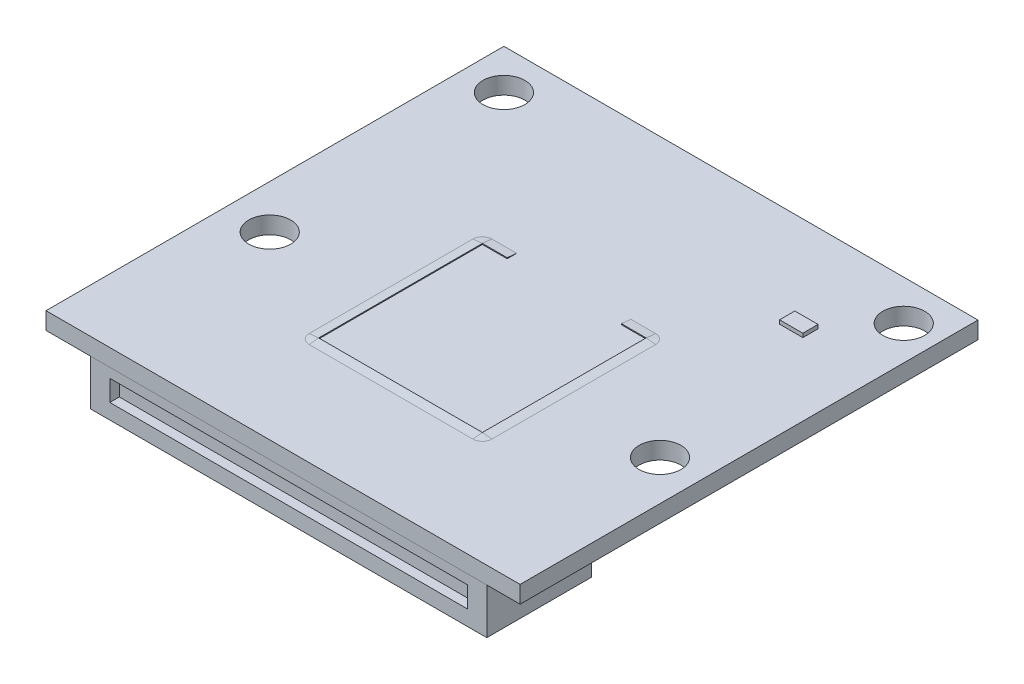
SolidWorks part; units mm, degrees
ref_plane "Front" through (0, 0, 0) normal (0, 0, 1) x (1, 0, 0)
ref_plane "Top" through (0, 0, 0) normal (0, 1, 0) x (1, 0, 0)
ref_plane "Right" through (0, 0, 0) normal (1, 0, 0) x (0, 0, -1)
sketch "Skizze1" plane through (0, 0, 0) normal (0, 1, 0) x (1, 0, 0)
  line L0 (-0.3, 13.88) -> (-0.3, -10.17) construction
  line L1 (-12.75, 13.88) -> (12.15, 13.88)
  line L2 (-12.75, 13.88) -> (-12.75, -10.17)
  line L3 (-12.75, -10.17) -> (12.15, -10.17)
  line L4 (12.15, 13.88) -> (12.15, -10.17)
  line L5 (0, 4.3) -> (0, -4.3) construction
  line L6 (-4.3, 0) -> (4.3, 0) construction
  line L7 (-4.3, 4.3) -> (4.3, 4.3) construction
  line L8 (-4.3, 4.3) -> (-4.3, -4.3) construction
  line L9 (-4.3, -4.3) -> (4.3, -4.3) construction
  line L10 (4.3, 4.3) -> (4.3, -4.3) construction
  circle A0 centre (-10.65, 11.78) radius 1.1
  circle A1 centre (10.35, 11.78) radius 1.1
  circle A2 centre (-10.45, -0.72) radius 1.1
  circle A3 centre (10.05, -0.72) radius 1.1
  dimension "D4" = 2.2
  dimension "D1" = 24.05
  dimension "D2" = 24.9
  dimension "D5" = 21
  dimension "D7" = 20.5
  dimension "D8" = 1.8
  dimension "D9" = 2.1
  dimension "D10" = 2.1
  dimension "D11" = 12.5
  dimension "D12" = 16.45
  dimension "D13" = 17.05
  dimension "D14" = 18.18
extrude "PCB" add sketch "Skizze1" against normal blind 0.9
sketch "Sketch4" plane through (0, 0, 0) normal (0, 1, 0) x (1, 0, 0)
  line L0 (-4.3, 4.3) -> (4.3, 4.3) construction
  line L1 (4.3, 4.3) -> (4.3, -4.3) construction
  line L2 (-4.3, -4.3) -> (4.3, -4.3) construction
  line L3 (-4.3, 4.3) -> (-4.3, -4.3) construction
  line L4 (-4.3, 4.3) -> (-3, 4.3)
  line L5 (4.3, 4.3) -> (4.3, -4.3)
  line L6 (-4.3, -4.3) -> (4.3, -4.3)
  line L7 (-4.3, 4.3) -> (-4.3, -4.3)
  line L8 (-4.8, 4.8) -> (-3, 4.8)
  line L9 (4.8, 4.8) -> (4.8, -4.8)
  line L10 (-4.8, -4.8) -> (4.8, -4.8)
  line L11 (-4.8, 4.8) -> (-4.8, -4.8)
  line L12 (-3, 4.8) -> (-3, 4.3)
  line L13 (3, 4.8) -> (3, 4.3)
  line L14 (0, 0) -> (0, 4.3) construction
  line L15 (3, 4.3) -> (4.3, 4.3)
  line L16 (-4.3, 4.3) -> (4.3, 4.3) construction
  line L17 (3, 4.8) -> (4.8, 4.8)
  line L18 (-4.8, 4.8) -> (4.8, 4.8) construction
  dimension "D2" = 6
  dimension "D1" = 0.5
extrude "Boss-Extrude1" add sketch "Sketch4" along normal blind 0.05
sketch "Skizze3" plane through (0, -0.9, 0) normal (0, -1, 0) x (1, 0, 0)
  line L0 (0, 4.67) -> (0, 0) construction
  line L1 (-10.4, 10.17) -> (10.4, 10.17)
  line L2 (-10.4, 10.17) -> (-10.4, 4.67)
  line L3 (-10.4, 4.67) -> (10.4, 4.67)
  line L4 (10.4, 10.17) -> (10.4, 4.67)
  line L5 (-12.75, 10.17) -> (12.15, 10.17) construction
  dimension "D1" = 20.8
  dimension "D2" = 5.5
extrude "Connector_closed" add sketch "Skizze3" along normal blind 2.4
sketch "Esquisse1" plane through (0, 0, 0) normal (0, 1, 0) x (1, 0, 0)
  line L0 (12.15, 13.88) -> (-12.75, 13.88) construction
  line L1 (8.35, 8.48) -> (7.13, 8.48)
  line L2 (8.35, 8.48) -> (8.35, 9.28)
  line L3 (8.35, 9.28) -> (7.13, 9.28)
  line L4 (7.13, 8.48) -> (7.13, 9.28)
  line L5 (12.15, -10.17) -> (12.15, 13.88) construction
  dimension "D1" = 1.22
  dimension "D2" = 0.8
  dimension "D3" = 4.6
  dimension "D4" = 3.8
extrude "Status LED" add sketch "Esquisse1" along normal blind 0.2
sketch "Esquisse3" plane through (0, 0, 10.17) normal (0, 0, 1) x (1, 0, 0)
  line L0 (-10.4, -3.3) -> (-10.4, -0.9) construction
  line L1 (-9.4, -1.4) -> (9.4, -1.4)
  line L2 (-9.4, -1.4) -> (-9.4, -2.5)
  line L3 (-9.4, -2.5) -> (9.4, -2.5)
  line L4 (9.4, -1.4) -> (9.4, -2.5)
  line L5 (10.4, -3.3) -> (10.4, -0.9) construction
  line L6 (10.4, -3.3) -> (-10.4, -3.3) construction
  line L7 (-12.75, 0) -> (12.15, 0) construction
  dimension "D1" = 1
  dimension "D2" = 1
  dimension "D3" = 0.8
  dimension "D4" = 1.4
extrude "Enlèv. mat.-Extru.1" cut sketch "Esquisse3" against normal blind 0.5
fillet "Fillet1" radius 0.5 4 edges at (4.8, 0.025, -4.8) (4.8, 0.025, 4.8) (-4.8, 0.025, 4.8) (-4.8, 0.025, -4.8)
chamfer "Chamfer1" distance 0.05 distance2 0.5 9 edges at (3.65, 0.05, -4.8) (4.8, 0.05, 0) (0, 0.05, 4.8) (-4.8, 0.05, 0) (-3.65, 0.05, -4.8) (4.6536, 0.05, -4.6536) (4.6536, 0.05, 4.6536) (-4.6536, 0.05, 4.6536) (-4.6536, 0.05, -4.6536) first distance on face at (3.65, 0.025, -4.8) first distance on face at (4.8, 0.025, 0) first distance on face at (0, 0.025, 4.8) first distance on face at (-4.8, 0.025, 0) first distance on face at (-3.65, 0.025, -4.8) first distance on face at (4.6018, 0.025, -4.6018) first distance on face at (4.6018, 0.025, 4.6018) first distance on face at (-4.6018, 0.025, 4.6018) first distance on face at (-4.6018, 0.025, -4.6018)
sketch "Sketch1" plane through (0, 0, 10.17) normal (0, 0, 1) x (1, 0, 0)
  line L0 (-10.4, -0.9) -> (10.4, -0.9)
split line "Split Line1"
